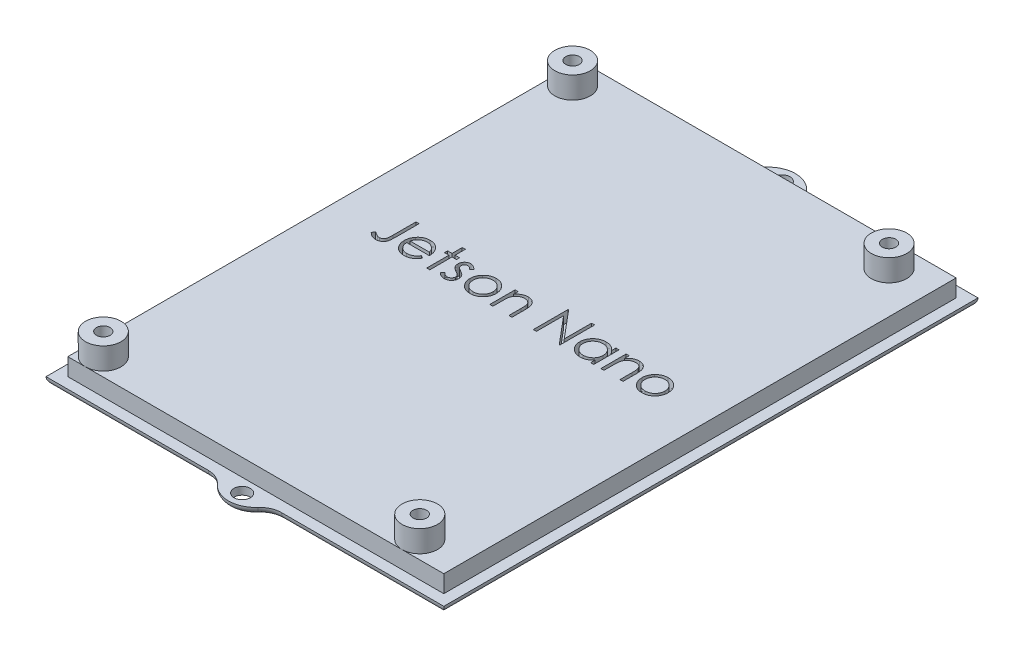
SolidWorks part; units mm, degrees
ref_plane "Front Plane" through (0, 0, 0) normal (0, 0, 1) x (1, 0, 0)
ref_plane "Top Plane" through (0, 0, 0) normal (0, 1, 0) x (1, 0, 0)
ref_plane "Right Plane" through (0, 0, 0) normal (1, 0, 0) x (0, 0, -1)
sketch "Sketch1" plane through (0, 0, 0) normal (0, 1, 0) x (1, 0, 0)
  line L0 (-34.45, 46.95) -> (34.45, 46.95)
  line L5 (-34.45, 46.95) -> (-34.45, -46.95)
  line L6 (-34.45, -46.95) -> (34.45, -46.95)
  line L7 (34.45, 46.95) -> (34.45, -46.95)
  point P11 (-34.45, 0)
  point P12 (0, -46.95)
  dimension "D3" = 93.9
  dimension "D4" = 68.9
extrude "Boss-Extrude1" add sketch "Sketch1" along normal blind 4.575
sketch "Sketch8" plane through (0, 4.575, 0) normal (0, 1, 0) x (1, 0, 0)
  line L0 (-34.45, -46.95) -> (34.45, -46.95) construction
  line L1 (-34.45, 46.95) -> (-34.45, -46.95) construction
  circle A0 centre (-31.2, -43.7) radius 1.25
  circle A1 centre (-31.2, 42.3) radius 1.25
  circle A2 centre (26.8, 42.3) radius 1.25
  circle A3 centre (26.8, -43.7) radius 1.25
  circle A4 centre (-31.2, 42.3) radius 3.25
  circle A5 centre (26.8, 42.3) radius 3.25
  circle A6 centre (26.8, -43.7) radius 3.25
  circle A7 centre (-31.2, -43.7) radius 3.25
  dimension "D3" = 2.5
  dimension "D4" = 2
  dimension "D1" = 58
  dimension "D2" = 86
extrude "Boss-Extrude5" add sketch "Sketch8" along normal blind 4
sketch "Sketch3" plane through (0, 4.575, 0) normal (0, 1, 0) x (1, 0, 0)
  circle A5 centre (-31.2, -43.7) radius 1.25 construction
  circle A6 centre (-31.2, 42.3) radius 1.25
  circle A7 centre (26.8, 42.3) radius 1.25
  circle A8 centre (26.8, -43.7) radius 1.25
  circle A9 centre (-31.2, -43.7) radius 1.25
extrude "Cut-Extrude1" cut sketch "Sketch3" against normal offset from surface (3.575 mm away) 1 up to face at (0, 0, 0)
sketch "Sketch9" plane through (0, 0, 0) normal (0, -1, 0) x (1, 0, 0)
  line L8 (-36.45, 48.95) -> (-36.45, -48.95)
  line L9 (-36.45, -48.95) -> (36.45, -48.95)
  line L10 (36.45, -48.95) -> (36.45, 48.95)
  line L11 (36.45, 48.95) -> (-36.45, 48.95)
  line L12 (-36.45, 48.95) -> (-36.45, -48.95)
  line L13 (-36.45, -48.95) -> (36.45, -48.95)
  line L14 (36.45, -48.95) -> (36.45, 48.95)
  line L15 (36.45, 48.95) -> (-36.45, 48.95)
  dimension "D1" = 2
extrude "Boss-Extrude6" add sketch "Sketch9" against normal blind 1.4
sketch "Sketch4" plane through (0, 0, 0) normal (0, 1, 0) x (1, 0, 0)
  line L2 (36.45, -48.95) -> (-36.45, -48.95) construction
  line L4 (34.45, -46.95) -> (-34.45, -46.95) construction
  line L5 (-6.7082, -48.95) -> (6.7082, -48.95)
  arc A3 (-6.7082, -48.95) -> (-3.7268, -50.2833) centre (-6.7082, -52.95) cw
  arc A4 (-3.7268, -50.2833) -> (3.7268, -50.2833) centre (0, -46.95) ccw
  arc A5 (3.7268, -50.2833) -> (6.7082, -48.95) centre (6.7082, -52.95) cw
  dimension "D1" = 5
  dimension "D2" = 4
extrude "Boss-Extrude3" add sketch "Sketch4" along normal blind 1.4
sketch "Sketch10" plane through (0, 1.4, 0) normal (0, 1, 0) x (1, 0, 0)
  line L0 (0, -46.95) -> (0, -51.95) construction
  line L1 (34.45, -46.95) -> (-34.45, -46.95) construction
  arc A0 (-3.7268, -50.2833) -> (3.7268, -50.2833) centre (0, -46.95) ccw construction
  circle A1 centre (0, -49.45) radius 1.5
  dimension "D1" = 3
extrude "Cut-Extrude3" cut sketch "Sketch10" against normal up to next
mirror "Mirror1" about plane through (0, 0, 0) normal (0, 0, 1) of "Cut-Extrude3", "Boss-Extrude3"
sketch "Sketch5" plane through (0, 4.575, 0) normal (0, 1, 0) x (1, 0, 0)
  line L0 (-30, 0) -> (30, 0) construction
  text T0 "Jetson Nano" font "Century Gothic" height in points 24
  point P6 (0, 0)
  dimension "D1" = 60
extrude "Cut-Extrude2" cut sketch "Sketch5" against normal blind 2
fillet "Fillet1" radius 1.4 12 edges at (36.45, 0, 0) (21.5791, 0, -48.95) (5.0752, 0, -49.2985) (0, 0, -51.95) (-5.0752, 0, -49.2985) (-21.5791, 0, -48.95) (-36.45, 0, 0) (-21.5791, 0, 48.95) (-5.0752, 0, 49.2985) (0, 0, 51.95) (5.0752, 0, 49.2985) (21.5791, 0, 48.95)
